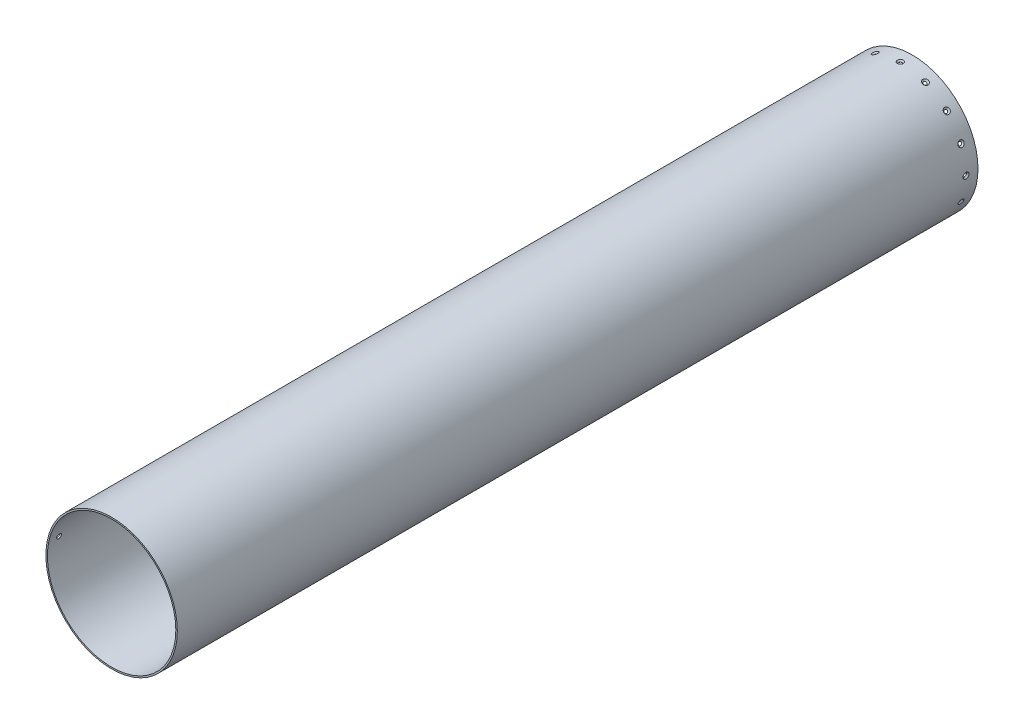
SolidWorks part; units mm, degrees
material "6061-T6 (SS)"
ref_plane "Front Plane" through (0, 0, 0) normal (0, 0, 1) x (1, 0, 0)
ref_plane "Top Plane" through (0, 0, 0) normal (0, 1, 0) x (1, 0, 0)
ref_plane "Right Plane" through (0, 0, 0) normal (1, 0, 0) x (0, 0, -1)
sketch "Sketch1" plane through (0, 0, 0) normal (0, 0, 1) x (1, 0, 0)
  circle A0 centre (0, 0) radius 69.85
  circle A1 centre (0, 0) radius 68.2625
  dimension "D1" = 139.7
  dimension "D2" = 1.5875
extrude "Extrude1" add sketch "Sketch1" along normal blind 850.9
ref_plane "Plane1" through (0, 0, 12.7) normal (0, 0, -1) x (-1, 0, 0)
sketch "Sketch2" plane through (0, 0, 12.7) normal (0, 0, -1) x (-1, 0, 0)
  line L0 (0, 0) -> (0, -69.85) construction
  circle A0 centre (0, 0) radius 69.85 construction
ref_plane "Plane2" through (0, -69.85, 12.7) normal (0, -1, 0) x (1, 0, 0)
hole_wizard "CSK for M3 Flat Head Machine Screw1" positions "Sketch5" profile "Sketch4" countersink size "M3" standard "Ansi Metric" end condition through all
sketch "Sketch5" plane through (0, -69.85, 12.7) normal (0, -1, 0) x (1, 0, 0)
  point P2 (0, 0)
sketch "Sketch4" plane through (0, -69.85, 12.7) normal (1, 0, 0) x (0, 0, -1)
  line L0 (0, 0) -> (0, 161.1134)
  line L1 (0, 161.1134) -> (1.7, 161.1134)
  line L2 (1.7, 161.1134) -> (1.7, 1.45)
  line L3 (1.7, 1.45) -> (3.15, 0)
  line L5 (3.15, 0) -> (0, 0)
  line L6 (-1.7, 1.45) -> (-3.15, 0) construction
  line L11 (0, -6.35) -> (0, 107.95) construction
  dimension "Thru Hole Dia." = 3.4
  dimension "Thru Hole Depth" = 161.1134
  dimension "Near C'Sink Dia." = 6.3
  dimension "Near C'Sink Angle" = 90
pattern_circular "CirPattern1" count 16 over 360 about axis through (0, 0, 850.9) along (0, 0, -1) of "CSK for M3 Flat Head Machine Screw1"
ref_plane "Plane3" through (0, 0, 839.7875) normal (0, 0, 1) x (1, 0, 0)
ref_plane "Plane5" through (0, 0, 0) normal (0.8315, 0.5556, 0) x (-0.5556, 0.8315, 0)
ref_plane "Plane7" through (0, 0, 0) normal (0.5556, -0.8315, 0) x (0.8315, 0.5556, 0)
ref_plane "Plane9" through (0, 0, 0) normal (-0.1951, -0.9808, 0) x (0.9808, -0.1951, 0)
sketch "Sketch7" plane through (0, 0, 850.9) normal (0, 0, 1) x (1, 0, 0)
  circle A0 centre (0, 0) radius 69.85 construction
  point P0 (69.85, 0)
ref_plane "Plane8" through (-68.5079, 13.6271, 425.45) normal (-0.9808, 0.1951, 0) x (0.1951, 0.9808, 0)
sketch "Sketch8" plane through (-68.5079, 13.6271, 425.45) normal (-0.9808, 0.1951, 0) x (0.1951, 0.9808, 0)
  line L0 (0, -425.45) -> (0, -414.3248) construction
hole_wizard "#7 (0.201) Diameter Hole1" positions "Sketch10" profile "Sketch9" hole size "#7" standard "Ansi Inch"
sketch "Sketch10" plane through (-68.5079, 13.6271, 425.45) normal (-0.9808, 0.1951, 0) x (0.1951, 0.9808, 0)
  point P1 (0, -414.3248)
sketch "Sketch9" plane through (-68.5079, 13.6271, 839.7748) normal (0, 0, 1) x (-0.1951, -0.9808, 0)
  line L0 (0, 0) -> (0, 11.6938)
  line L1 (0, 11.6938) -> (2.5527, 10.16)
  line L2 (2.5527, 10.16) -> (2.5527, 0)
  line L5 (2.5527, 0) -> (0, 0)
  line L10 (0, 11.6938) -> (-2.5527, 10.16) construction
  line L11 (0, -6.35) -> (0, 107.95) construction
  dimension "Hole Dia." = 5.1054
  dimension "Hole Depth" = 10.16
  dimension "Drill Angle" = 118
